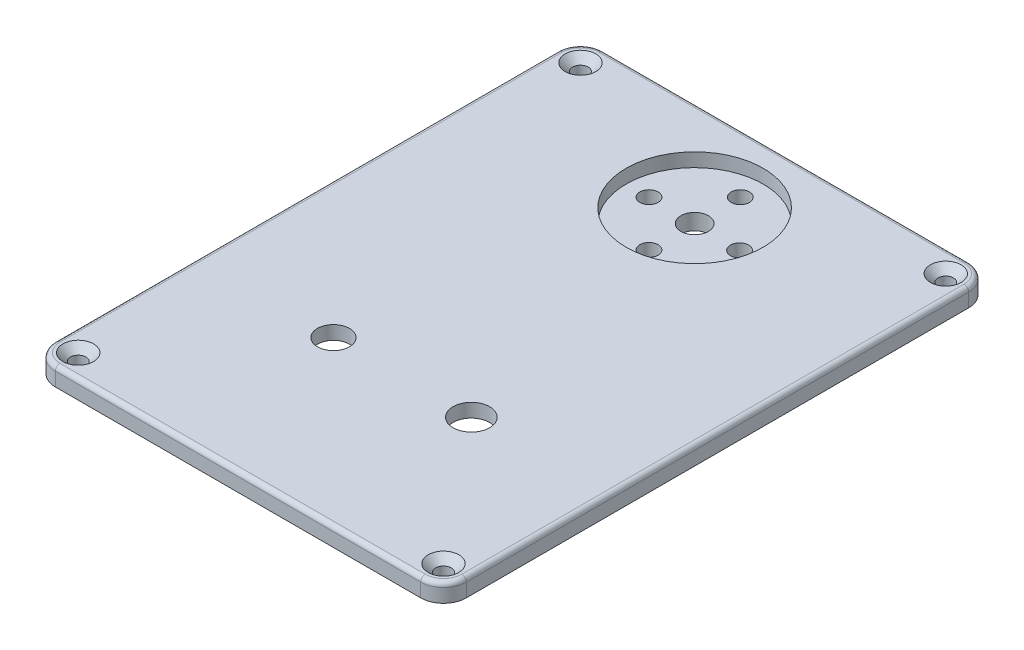
SolidWorks part; units mm, degrees
ref_plane "前视基准面" through (0, 0, 0) normal (0, 0, 1) x (1, 0, 0)
ref_plane "上视基准面" through (0, 0, 0) normal (0, 1, 0) x (1, 0, 0)
ref_plane "右视基准面" through (0, 0, 0) normal (1, 0, 0) x (0, 0, -1)
sketch "草图2" plane through (0, 0, 0) normal (0, 1, 0) x (1, 0, 0)
  line L1 (-45, 60) -> (45, 60)
  line L2 (-45, 60) -> (-45, -60)
  line L3 (-45, -60) -> (45, -60)
  line L4 (45, 60) -> (45, -60)
  line L5 (0, -60) -> (0, 60) construction
  line L6 (-45, 0) -> (45, 0) construction
  circle A0 centre (0, 40) radius 15
  point P0 (0, 0)
  dimension "D3" = 20
  dimension "D1" = 120
  dimension "D2" = 90
extrude "凸台-拉伸1" add sketch "草图2" along normal blind 3
sketch "草图3" plane through (0, 0, 0) normal (0, -1, 0) x (1, 0, 0)
  line L0 (-42, -50) -> (-42, 50)
  line L1 (-35, -57) -> (35, -57)
  line L3 (-45, 60) -> (45, 60)
  line L4 (42, -50) -> (42, 50)
  line L5 (0, 55) -> (0, -55) construction
  line L6 (-40, 0) -> (40, 0) construction
  line L7 (-45, 60) -> (-45, -60)
  line L8 (-45, -60) -> (45, -60)
  line L9 (-42, 50) -> (-35, 50)
  line L10 (-35, 57) -> (-35, 50)
  line L11 (45, 60) -> (45, -60)
  line L12 (0, -60) -> (0, 60) construction
  line L13 (42, 50) -> (35, 50)
  line L14 (35, 57) -> (35, 50)
  line L15 (-45, 0) -> (45, 0) construction
  line L17 (42, -50) -> (35, -50)
  line L18 (35, -57) -> (35, -50)
  line L21 (-42, -50) -> (-35, -50)
  line L22 (-35, -57) -> (-35, -50)
  line L23 (-35, 57) -> (35, 57)
  line L27 (0, 60) -> (0, -60) construction
  line L28 (-45, 0) -> (45, 0) construction
  line L33 (0, -60) -> (0, 60) construction
  line L34 (45, 0) -> (-45, 0) construction
  point P0 (0, 0)
  point P1 (0, 0)
  point P4 (0, 0)
  point P34 (0, 0)
  dimension "D11" = 7
  dimension "D1" = 120
  dimension "D2" = 90
  dimension "D3" = 7
  dimension "D4" = 7
  dimension "D5" = 3
  dimension "D6" = 7
  dimension "D7" = 7
  dimension "D8" = 3
  dimension "D9" = 7
  dimension "D10" = 7
  dimension "D12" = 7
  dimension "D13" = 3
  dimension "D14" = 7
extrude "凸台-拉伸2" add sketch "草图3" along normal blind 1 separate body
sketch "草图8" plane through (0, 0, 0) normal (0, -1, 0) x (1, 0, 0)
  line L0 (-5.9161, -57) -> (5.9161, -57)
  line L1 (-35, -57) -> (35, -57) construction
  circle A0 centre (0, -40) radius 3
  arc A2 (5.9161, -57) -> (-5.9161, -57) centre (0, -40) ccw
extrude "凸台-拉伸5" add sketch "草图8" along normal blind 3.5
sketch "草图10" plane through (0, 0, 0) normal (0, 1, 0) x (1, 0, 0)
  circle A0 centre (0, 30) radius 2
  circle A1 centre (10, 39.8374) radius 2
  circle A2 centre (0, 50) radius 2
  circle A3 centre (-10, 40) radius 2
  circle A4 centre (0, 40) radius 3 construction
  dimension "D1" = 10
  dimension "D3" = 10
  dimension "D4" = 10
  dimension "D5" = 0.1626
  dimension "D2" = 10
extrude "切除-拉伸2" cut sketch "草图10" against normal blind 3.1
hole_wizard "M3 六角凹锥坑螺钉的锥形沉头孔3" positions "草图14" profile "草图15" countersink size "M3" standard "ISO" end condition through all
sketch "草图14" plane through (0, 3, 0) normal (0, 1, 0) x (1, 0, 0)
  line L0 (-45, -60) -> (45, -60) construction
  line L3 (45, -60) -> (45, 60) construction
  line L4 (-45, 60) -> (-45, -60) construction
  line L5 (45, 60) -> (-45, 60) construction
  point P0 (-40, -55)
  point P2 (-40, 55)
  point P4 (40, 55)
  point P6 (40, -55)
  dimension "D1" = 5
  dimension "D2" = 5
  dimension "D3" = 5
  dimension "D4" = 5
  dimension "D5" = 5
  dimension "D6" = 5
  dimension "D7" = 5
  dimension "D8" = 5
sketch "草图15" plane through (-40, 3, 55) normal (1, 0, 0) x (0, 0, 1)
  line L0 (0, 0) -> (0, 6.5)
  line L1 (0, 6.5) -> (1.7, 6.5)
  line L2 (1.7, 6.5) -> (1.7, 1.66)
  line L3 (1.7, 1.66) -> (3.36, 0)
  line L5 (3.36, 0) -> (0, 0)
  line L6 (-1.7, 1.66) -> (-3.36, 0) construction
  line L11 (0, -6.35) -> (0, 107.95) construction
  dimension "通孔孔直径" = 3.4
  dimension "通孔孔深度" = 6.5
  dimension "近端锥形沉头孔直径" = 6.72
  dimension "近端锥形沉头孔角度" = 90
fillet "圆角2" radius 5 1 edges at (35, -0.5, -50)
fillet "圆角3" radius 5 1 edges at (35, -0.5, 50)
fillet "圆角4" radius 5 1 edges at (-35, -0.5, 50)
fillet "圆角5" radius 5 1 edges at (-35, -0.5, -50)
fillet "圆角6" radius 5 1 edges at (-45, 1, -60)
fillet "圆角7" radius 5 1 edges at (45, 1, -60)
fillet "圆角8" radius 5 1 edges at (45, 1, 60)
fillet "圆角9" radius 5 1 edges at (-45, 1, 60)
fillet "圆角10" radius 1 8 edges at (-43.5355, 3, 58.5355) (-45, 3, 0) (-43.5355, 3, -58.5355) (0, 3, -60) (43.5355, 3, -58.5355) (45, 3, 0) (43.5355, 3, 58.5355) (0, 3, 60)
fillet "圆角11" radius 2 1 edges at (0, -3.5, -22)
sketch "草图16" plane through (0, 3, 0) normal (0, 1, 0) x (1, 0, 0)
  circle A0 centre (-14.923, -24.182) radius 3.5
  circle A1 centre (15.277, -24.182) radius 4
extrude "切除-拉伸3" cut sketch "草图16" against normal blind 3
